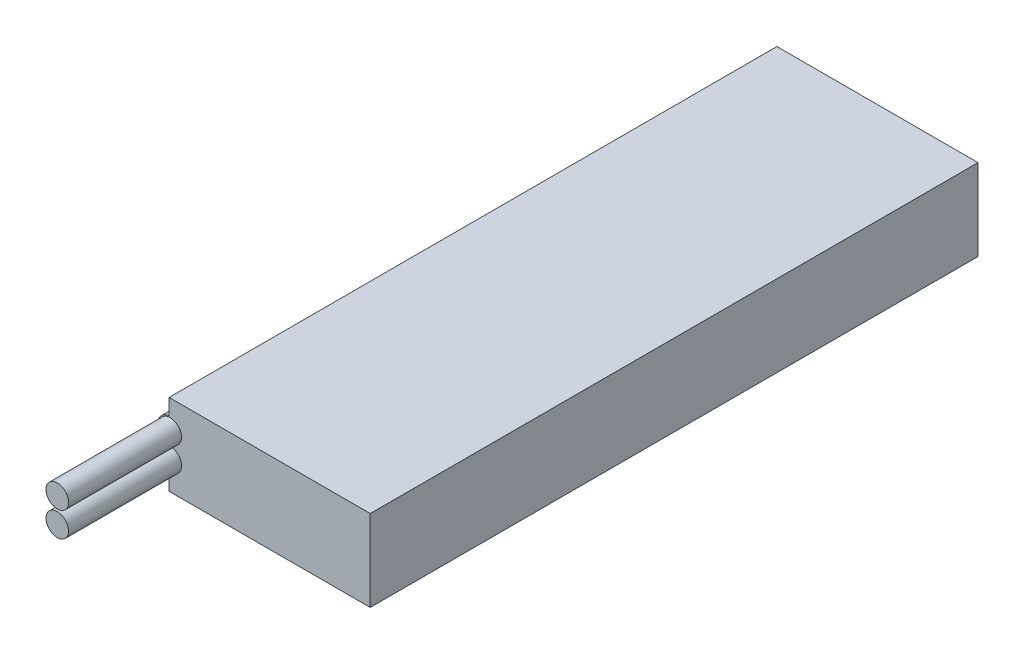
SolidWorks part; units mm, degrees
ref_plane "Front Plane" through (0, 0, 0) normal (0, 0, 1) x (1, 0, 0)
ref_plane "Top Plane" through (0, 0, 0) normal (0, 1, 0) x (1, 0, 0)
ref_plane "Right Plane" through (0, 0, 0) normal (1, 0, 0) x (0, 0, -1)
sketch "Sketch1" plane through (0, 0, 0) normal (0, 1, 0) x (1, 0, 0)
  line L1 (-22.25, -67.25) -> (22.25, -67.25)
  line L2 (-22.25, -67.25) -> (-22.25, 67.25)
  line L3 (-22.25, 67.25) -> (22.25, 67.25)
  line L4 (22.25, -67.25) -> (22.25, 67.25)
  line L5 (-22.25, -67.25) -> (22.25, 67.25) construction
  line L6 (-22.25, 67.25) -> (22.25, -67.25) construction
  point P0 (0, 0)
  dimension "D1" = 44.5
  dimension "D2" = 134.5
extrude "Boss-Extrude1" add sketch "Sketch1" along normal blind 18
sketch "Imagen" plane through (0, 18, 0) normal (0, 1, 0) x (1, 0, 0)
  line L0 (105.6667, 103.5) -> (539.1806, 103.5) construction
  line L1 (19, -59) -> (19, 75.5) construction
sketch "Sketch3" plane through (0, 0, 67.25) normal (0, 0, 1) x (1, 0, 0)
  line L0 (-22, 11.75) -> (-22, 6.25) construction
  line L1 (-24.75, 20.8788) -> (-24.75, -9.3152) construction
  line L3 (22.25, 18) -> (22.25, 0) construction
  line L4 (-22, 9) -> (22.25, 9) construction
  line L5 (-22.25, 14.4886) -> (-22.25, 3.5114)
  line L6 (-22.25, 18) -> (-22.25, 0) construction
  line L7 (-24.75, 11.75) -> (-24.75, 6.25)
  circle A0 centre (-22, 11.75) radius 2.75 construction
  circle A1 centre (-22, 6.25) radius 2.75 construction
  arc A2 (-22.25, 14.4886) -> (-24.75, 11.75) centre (-22, 11.75) ccw
  arc A3 (-22.25, 3.5114) -> (-24.75, 6.25) centre (-22, 6.25) cw
  line M9 (-22.25, 18) -> (-22.25, 0)
  dimension "D1" = 5.5
  dimension "D2" = 47
extrude "Boss-Extrude2" add sketch "Sketch3" against normal offset from surface (7 mm away) 127.5 contours A1 M9 | A0 M9 | A0 M9 | A1 M9 region at (-23.4148, 9, 67.25) up to face at (0, 9, -67.25)
sketch "Sketch5" plane through (0, 0, 67.25) normal (0, 0, 1) x (1, 0, 0)
  arc A2 (-24.75, 6.25) -> (-22.25, 3.5114) centre (-22, 6.25) ccw construction
  arc A3 (-22.25, 14.4886) -> (-24.75, 11.75) centre (-22, 11.75) ccw construction
  circle A4 centre (-22, 6.25) radius 2.75 construction
  circle A5 centre (-22, 11.75) radius 2.75 construction
  circle A6 centre (-22, 11.75) radius 2.5
  circle A7 centre (-22, 6.25) radius 2.5
  dimension "D1" = 0.25
  dimension "D2" = 0.25
extrude "Boss-Extrude4" add sketch "Sketch5" along normal blind 25
